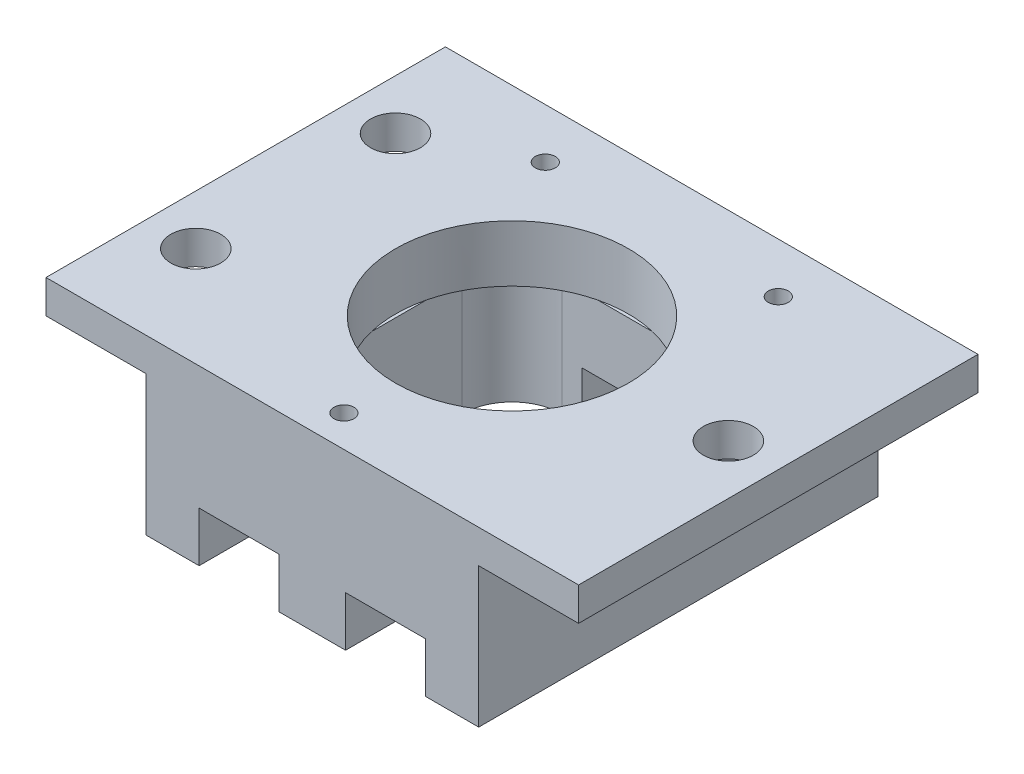
SolidWorks part; units mm, degrees
ref_plane "前视基准面" through (0, 0, 0) normal (0, 0, 1) x (1, 0, 0)
ref_plane "上视基准面" through (0, 0, 0) normal (0, 1, 0) x (1, 0, 0)
ref_plane "右视基准面" through (0, 0, 0) normal (1, 0, 0) x (0, 0, -1)
other "Configuration Table"
sketch "草图1" plane through (0, 0, 0) normal (0, 1, 0) x (1, 0, 0)
  line L7 (-5, -6) -> (5, -6)
  line L8 (-5, -6) -> (-5, 6)
  line L9 (-5, 6) -> (5, 6)
  line L10 (5, -6) -> (5, 6)
  circle A0 centre (0, 0) radius 3.5
  point P0 (0, 0)
  point P5 (0, 0)
  dimension "D1" = 7
  dimension "D2" = 10
  dimension "D3" = 6
  dimension "D4" = 6
  dimension "D5" = 5
extrude "凸台-拉伸1" add sketch "草图1" along normal blind 1.7 contours L9 L10 L7 L8 | A0
sketch "草图4" plane through (0, 0, 0) normal (0, -1, 0) x (1, 0, 0)
  line L0 (-5, 6) -> (5, 6) construction
  line L1 (3.4, -3.4) -> (-3.4, -3.4)
  line L2 (3.4, -3.4) -> (3.4, 4.1)
  line L3 (3.4, 4.1) -> (-3.4, 4.1)
  line L4 (-3.4, -3.4) -> (-3.4, 4.1)
  line L5 (-5, 6) -> (5, 6)
  line L6 (-5, 6) -> (-5, -6)
  line L7 (-5, -6) -> (5, -6)
  line L8 (5, 6) -> (5, -6)
  line L9 (-5, -6) -> (5, -6) construction
  line L11 (-3.4, 4.1) -> (-1, 4.1)
  line L12 (-3.4, 4.1) -> (-3.4, 6)
  line L13 (-3.4, 6) -> (-1, 6)
  line L14 (-1, 4.1) -> (-1, 6)
  line L15 (3.4, 4.1) -> (1, 4.1)
  line L16 (3.4, 4.1) -> (3.4, 6)
  line L17 (3.4, 6) -> (1, 6)
  line L18 (1, 4.1) -> (1, 6)
  line L19 (-1.3, -3.4) -> (1.3, -3.4)
  line L20 (-1.3, -3.4) -> (-1.3, -6)
  line L21 (-1.3, -6) -> (1.3, -6)
  line L22 (1.3, -3.4) -> (1.3, -6)
  line L23 (-8, 6) -> (8, 6)
  line L24 (-8, 6) -> (-8, -6)
  line L25 (-8, -6) -> (8, -6)
  line L26 (8, 6) -> (8, -6)
  circle A0 centre (-1.9, -1.9) radius 1.5
  circle A1 centre (1.9, -1.9) radius 1.5
  line M5 (-5, 6) -> (-5, -6)
  line M7 (5, -6) -> (5, 6)
  circle M9 centre (0, 0) radius 3.5
  dimension "D5" = 3
  dimension "D1" = 3.4
  dimension "D2" = 4.1
  dimension "D3" = 3.4
  dimension "D4" = 3.4
  dimension "D6" = 5
  dimension "D7" = 5
  dimension "D8" = 1
  dimension "D9" = 1
  dimension "D10" = 1.3
  dimension "D11" = 1.3
  dimension "D12" = 3
  dimension "D13" = 3
extrude "凸台-拉伸2" add sketch "草图4" along normal blind 3.5 contours A0 M9 | A0 M9 | A1 M9 | A1 M9 | A1 L2 L4 A0 L1 M9 | L4 L2 L3 M9 | A0 L4 M9 | A1 L2 M9 | A1 L1 M9 | A0 L1 M9 | L8 L7 L6 L5 region at (1.279, 0, -3.3571) region at (2.6319, 0, -2.6319) region at (3.3571, 0, -1.279) region at (0, 0, 0.7277) region at (1.7105, 0, -1.7105) region at (0, 0, 3.5755) region at (-1.279, 0, -3.3571) region at (-1.7105, 0, -1.7105) region at (-2.6319, 0, -2.6319) region at (-3.3571, 0, -1.279)
extrude "凸台-拉伸3" add sketch "草图4<4>" along normal blind 1 from surface contours L24 L25 L23 M5 | L26 L23 L25 M7 region at (6.5, 0, 0) region at (-6.5, 0, 0) starting at face at (0, 1.7, 0)
sketch "草图4<4>" plane through (0, 0, 0) normal (0, -1, 0) x (1, 0, 0) same geometry as "草图4"
extrude "切除-拉伸2" cut sketch "草图4<3>" against normal blind 1.5 from surface contours L3 L14 L5 L12 | L18 L3 L16 L5 | L22 L1 L20 L7 M9 | L1 M9 region at (0, 0, -4.721) region at (0, 0, -3.44) region at (2.2, 0, 5.05) region at (-2.2, 0, 5.05) starting at face at (0, -3.5, -0.5036)
sketch "草图4<3>" plane through (0, 0, 0) normal (0, -1, 0) x (1, 0, 0) same geometry as "草图4"
sketch "草图5" plane through (0, 1.7, 0) normal (0, 1, 0) x (1, 0, 0)
  line L9 (0, -4.1) -> (0, -6) construction
  line L10 (1, -4.1) -> (-1, -4.1) construction
  line L11 (-1, -6) -> (1, -6) construction
  line L12 (-5, 6) -> (-1.3, 6) construction
  line L13 (-5, -6) -> (-5, 6) construction
  line L14 (5, -6) -> (5, 6) construction
  circle A6 centre (3.5, 4.5) radius 0.3
  circle A7 centre (-3.5, 4.5) radius 0.3
  circle A8 centre (0, -5.05) radius 0.3
  circle A9 centre (6.5, 0) radius 0.75
  circle A10 centre (-6.5, 3) radius 0.75
  circle A11 centre (-6.5, -3) radius 0.75
  point P6 (-7.2181, -3)
  point P7 (13.0482, 3)
  point P8 (0, 0)
  point P9 (13.1403, 0)
  dimension "D1" = 1.5
  dimension "D2" = 6.5
  dimension "D3" = 0.6
  dimension "D4" = 1.5
  dimension "D5" = 1.5
  dimension "D6" = 1.5
  dimension "D7" = 3
  dimension "D8" = 3
  dimension "D9" = 6.5
extrude "切除-拉伸5" cut sketch "草图5" along normal blind 4 from surface contours A6 | A7 | A8 starting at face at (3.0872, -3.5, -1.2872)
extrude "切除-拉伸6" cut sketch "草图5<6>" against normal through all
sketch "草图5<6>" plane through (0, 1.7, 0) normal (0, 1, 0) x (1, 0, 0) same geometry as "草图5"
